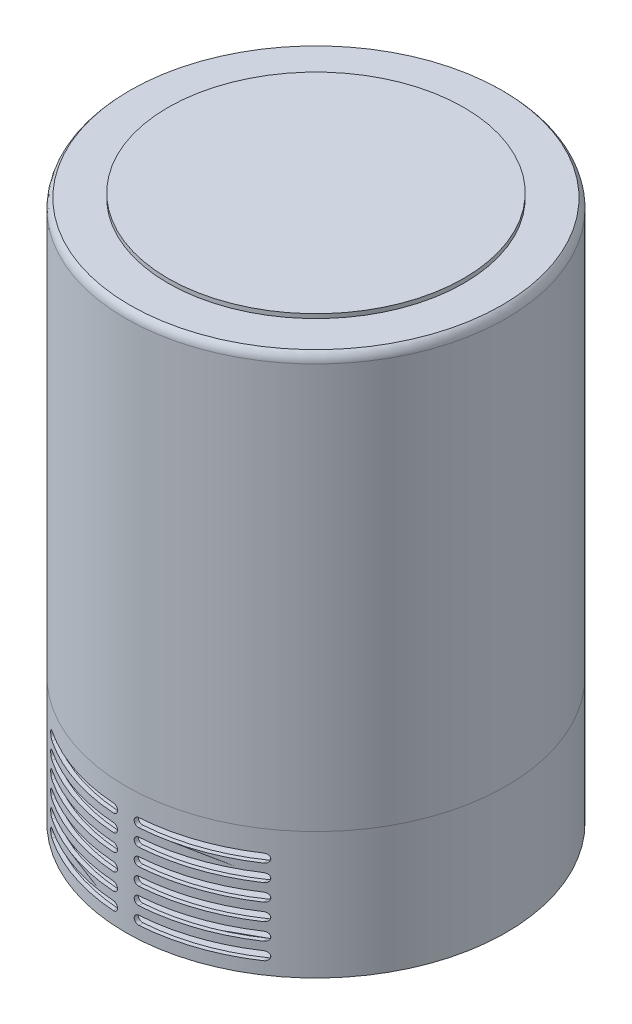
SolidWorks part; units mm, degrees
ref_plane "Front Plane" through (0, 0, 0) normal (0, 0, 1) x (1, 0, 0)
ref_plane "Top Plane" through (0, 0, 0) normal (0, 1, 0) x (1, 0, 0)
ref_plane "Right Plane" through (0, 0, 0) normal (1, 0, 0) x (0, 0, -1)
sketch "Sketch1" plane through (0, 0, 0) normal (0, 1, 0) x (1, 0, 0)
  circle A0 centre (0, 0) radius 45
  circle A1 centre (0, 0) radius 44
  dimension "D1" = 90
  dimension "D2" = 88
extrude "Boss-Extrude1" add sketch "Sketch1" along normal blind 98
fillet "Fillet1" radius 3 1 edges at (0, 98, 45)
sketch "Sketch13" plane through (0, 0, 0) normal (0, 1, 0) x (1, 0, 0)
  circle A0 centre (0, 0) radius 44
  dimension "D1" = 88
extrude "Boss-Extrude9" add sketch "Sketch13" along normal blind 2 from offset 96
sketch "Sketch5" plane through (0, 0, 0) normal (0, 1, 0) x (1, 0, 0)
  circle A0 centre (0, 0) radius 45
  dimension "D1" = 90
extrude "Boss-Extrude6" add sketch "Sketch5" against normal blind 30 separate body
sketch "Sketch6" plane through (0, 0, 0) normal (0, 1, 0) x (1, 0, 0)
  circle A0 centre (0, 0) radius 44
  dimension "D1" = 88
extrude "Cut-Extrude2" cut sketch "Sketch6" against normal blind 29
sketch "Sketch7" plane through (0, 98, 0) normal (0, 1, 0) x (1, 0, 0)
  circle A0 centre (0, 0) radius 35
  dimension "D1" = 70
extrude "Boss-Extrude7" add sketch "Sketch7" along normal blind 1
sketch "Sketch8" plane through (0, 0, 0) normal (1, 0, 0) x (0, 0, -1)
  line L0 (45, -15) -> (-47.6224, -15) construction
  line L1 (45, -30) -> (45, 0) construction
  line L3 (3.5, -16.75) -> (-3.5, -16.75)
  line L4 (3.5, -16.75) -> (3.5, -13.25)
  line L5 (3.5, -13.25) -> (-3.5, -13.25)
  line L6 (-3.5, -16.75) -> (-3.5, -13.25)
  line L7 (3.5, -16.75) -> (-3.5, -13.25) construction
  line L8 (3.5, -13.25) -> (-3.5, -16.75) construction
  point P4 (0, -15)
  dimension "D1" = 7
  dimension "D2" = 3.5
extrude "Cut-Extrude3" cut sketch "Sketch8" against normal through all from offset 39 offset against normal yes
sketch "Sketch10" plane through (0, 0, 0) normal (0, 0, 1) x (1, 0, 0)
  line L0 (25, -6.0288) -> (3, -6.0288) construction
  line L5 (0, 12.9357) -> (0, -57.2827) construction
  line L30 (25, -5) -> (3, -5)
  line L31 (25, -7.0576) -> (3, -7.0576)
  line L32 (-25, -6.0288) -> (-3, -6.0288) construction
  line L33 (-25, -5) -> (-3, -5)
  line L34 (-25, -7.0576) -> (-3, -7.0576)
  line L35 (-25, -10.0288) -> (-3, -10.0288) construction
  line L36 (-25, -9) -> (-3, -9)
  line L37 (-25, -11.0576) -> (-3, -11.0576)
  line L38 (25, -10.0288) -> (3, -10.0288) construction
  line L39 (25, -9) -> (3, -9)
  line L40 (25, -11.0576) -> (3, -11.0576)
  line L41 (-25, -14.0288) -> (-3, -14.0288) construction
  line L42 (-25, -13) -> (-3, -13)
  line L43 (-25, -15.0576) -> (-3, -15.0576)
  line L44 (25, -14.0288) -> (3, -14.0288) construction
  line L45 (25, -13) -> (3, -13)
  line L46 (25, -15.0576) -> (3, -15.0576)
  line L47 (-25, -18.0288) -> (-3, -18.0288) construction
  line L48 (-25, -17) -> (-3, -17)
  line L49 (-25, -19.0576) -> (-3, -19.0576)
  line L50 (25, -18.0288) -> (3, -18.0288) construction
  line L51 (25, -17) -> (3, -17)
  line L52 (25, -19.0576) -> (3, -19.0576)
  line L53 (-25, -22.0288) -> (-3, -22.0288) construction
  line L54 (-25, -21) -> (-3, -21)
  line L55 (-25, -23.0576) -> (-3, -23.0576)
  line L56 (25, -22.0288) -> (3, -22.0288) construction
  line L57 (25, -21) -> (3, -21)
  line L58 (25, -23.0576) -> (3, -23.0576)
  line L59 (-25, -26.0288) -> (-3, -26.0288) construction
  line L60 (-25, -25) -> (-3, -25)
  line L61 (-25, -27.0576) -> (-3, -27.0576)
  line L62 (25, -26.0288) -> (3, -26.0288) construction
  line L63 (25, -25) -> (3, -25)
  line L64 (25, -27.0576) -> (3, -27.0576)
  line L65 (45, 0) -> (-45, 0) construction
  arc A0 (-25, -5) -> (-25, -7.0576) centre (-25, -6.0288) ccw
  arc A1 (-3, -7.0576) -> (-3, -5) centre (-3, -6.0288) ccw
  arc A2 (25, -5) -> (25, -7.0576) centre (25, -6.0288) cw
  arc A3 (3, -7.0576) -> (3, -5) centre (3, -6.0288) cw
  arc A4 (-25, -9) -> (-25, -11.0576) centre (-25, -10.0288) ccw
  arc A5 (-3, -11.0576) -> (-3, -9) centre (-3, -10.0288) ccw
  arc A6 (25, -9) -> (25, -11.0576) centre (25, -10.0288) cw
  arc A7 (3, -11.0576) -> (3, -9) centre (3, -10.0288) cw
  arc A8 (-25, -13) -> (-25, -15.0576) centre (-25, -14.0288) ccw
  arc A9 (-3, -15.0576) -> (-3, -13) centre (-3, -14.0288) ccw
  arc A10 (25, -13) -> (25, -15.0576) centre (25, -14.0288) cw
  arc A11 (3, -15.0576) -> (3, -13) centre (3, -14.0288) cw
  arc A12 (-25, -17) -> (-25, -19.0576) centre (-25, -18.0288) ccw
  arc A13 (-3, -19.0576) -> (-3, -17) centre (-3, -18.0288) ccw
  arc A14 (25, -17) -> (25, -19.0576) centre (25, -18.0288) cw
  arc A15 (3, -19.0576) -> (3, -17) centre (3, -18.0288) cw
  arc A16 (-25, -21) -> (-25, -23.0576) centre (-25, -22.0288) ccw
  arc A17 (-3, -23.0576) -> (-3, -21) centre (-3, -22.0288) ccw
  arc A18 (25, -21) -> (25, -23.0576) centre (25, -22.0288) cw
  arc A19 (3, -23.0576) -> (3, -21) centre (3, -22.0288) cw
  arc A20 (-25, -25) -> (-25, -27.0576) centre (-25, -26.0288) ccw
  arc A21 (-3, -27.0576) -> (-3, -25) centre (-3, -26.0288) ccw
  arc A22 (25, -25) -> (25, -27.0576) centre (25, -26.0288) cw
  arc A23 (3, -27.0576) -> (3, -25) centre (3, -26.0288) cw
  point P3 (14, -6.0288)
  point P7 (-14, -6.0288)
  point P19 (14, -10.0288)
  point P22 (-14, -10.0288)
  point P33 (14, -14.0288)
  point P36 (-14, -14.0288)
  point P47 (14, -18.0288)
  point P50 (-14, -18.0288)
  point P61 (14, -22.0288)
  point P64 (-14, -22.0288)
  point P75 (14, -26.0288)
  point P78 (-14, -26.0288)
  dimension "D1" = 22
  dimension "D2" = 6
  dimension "D3" = 5
extrude "Cut-Extrude5" cut sketch "Sketch10" against normal blind 10 from offset 36 offset against normal yes
sketch "Sketch12" plane through (0, 0, 0) normal (0, 0, 1) x (1, 0, 0)
  line L0 (25, -6.0288) -> (3, -6.0288) construction
  line L5 (0, 12.9357) -> (0, -57.2827) construction
  line L30 (25, -5) -> (3, -5)
  line L31 (25, -7.0576) -> (3, -7.0576)
  line L32 (-25, -6.0288) -> (-3, -6.0288) construction
  line L33 (-25, -5) -> (-3, -5)
  line L34 (-25, -7.0576) -> (-3, -7.0576)
  line L35 (-25, -10.0288) -> (-3, -10.0288) construction
  line L36 (-25, -9) -> (-3, -9)
  line L37 (-25, -11.0576) -> (-3, -11.0576)
  line L38 (25, -10.0288) -> (3, -10.0288) construction
  line L39 (25, -9) -> (3, -9)
  line L40 (25, -11.0576) -> (3, -11.0576)
  line L41 (-25, -14.0288) -> (-3, -14.0288) construction
  line L42 (-25, -13) -> (-3, -13)
  line L43 (-25, -15.0576) -> (-3, -15.0576)
  line L44 (25, -14.0288) -> (3, -14.0288) construction
  line L45 (25, -13) -> (3, -13)
  line L46 (25, -15.0576) -> (3, -15.0576)
  line L47 (-25, -18.0288) -> (-3, -18.0288) construction
  line L48 (-25, -17) -> (-3, -17)
  line L49 (-25, -19.0576) -> (-3, -19.0576)
  line L50 (25, -18.0288) -> (3, -18.0288) construction
  line L51 (25, -17) -> (3, -17)
  line L52 (25, -19.0576) -> (3, -19.0576)
  line L53 (-25, -22.0288) -> (-3, -22.0288) construction
  line L54 (-25, -21) -> (-3, -21)
  line L55 (-25, -23.0576) -> (-3, -23.0576)
  line L56 (25, -22.0288) -> (3, -22.0288) construction
  line L57 (25, -21) -> (3, -21)
  line L58 (25, -23.0576) -> (3, -23.0576)
  line L59 (-25, -26.0288) -> (-3, -26.0288) construction
  line L60 (-25, -25) -> (-3, -25)
  line L61 (-25, -27.0576) -> (-3, -27.0576)
  line L62 (25, -26.0288) -> (3, -26.0288) construction
  line L63 (25, -25) -> (3, -25)
  line L64 (25, -27.0576) -> (3, -27.0576)
  line L65 (45, 0) -> (-45, 0) construction
  arc A0 (-25, -5) -> (-25, -7.0576) centre (-25, -6.0288) ccw
  arc A1 (-3, -7.0576) -> (-3, -5) centre (-3, -6.0288) ccw
  arc A2 (25, -5) -> (25, -7.0576) centre (25, -6.0288) cw
  arc A3 (3, -7.0576) -> (3, -5) centre (3, -6.0288) cw
  arc A4 (-25, -9) -> (-25, -11.0576) centre (-25, -10.0288) ccw
  arc A5 (-3, -11.0576) -> (-3, -9) centre (-3, -10.0288) ccw
  arc A6 (25, -9) -> (25, -11.0576) centre (25, -10.0288) cw
  arc A7 (3, -11.0576) -> (3, -9) centre (3, -10.0288) cw
  arc A8 (-25, -13) -> (-25, -15.0576) centre (-25, -14.0288) ccw
  arc A9 (-3, -15.0576) -> (-3, -13) centre (-3, -14.0288) ccw
  arc A10 (25, -13) -> (25, -15.0576) centre (25, -14.0288) cw
  arc A11 (3, -15.0576) -> (3, -13) centre (3, -14.0288) cw
  arc A12 (-25, -17) -> (-25, -19.0576) centre (-25, -18.0288) ccw
  arc A13 (-3, -19.0576) -> (-3, -17) centre (-3, -18.0288) ccw
  arc A14 (25, -17) -> (25, -19.0576) centre (25, -18.0288) cw
  arc A15 (3, -19.0576) -> (3, -17) centre (3, -18.0288) cw
  arc A16 (-25, -21) -> (-25, -23.0576) centre (-25, -22.0288) ccw
  arc A17 (-3, -23.0576) -> (-3, -21) centre (-3, -22.0288) ccw
  arc A18 (25, -21) -> (25, -23.0576) centre (25, -22.0288) cw
  arc A19 (3, -23.0576) -> (3, -21) centre (3, -22.0288) cw
  arc A20 (-25, -25) -> (-25, -27.0576) centre (-25, -26.0288) ccw
  arc A21 (-3, -27.0576) -> (-3, -25) centre (-3, -26.0288) ccw
  arc A22 (25, -25) -> (25, -27.0576) centre (25, -26.0288) cw
  arc A23 (3, -27.0576) -> (3, -25) centre (3, -26.0288) cw
  point P3 (14, -6.0288)
  point P7 (-14, -6.0288)
  point P19 (14, -10.0288)
  point P22 (-14, -10.0288)
  point P33 (14, -14.0288)
  point P36 (-14, -14.0288)
  point P47 (14, -18.0288)
  point P50 (-14, -18.0288)
  point P61 (14, -22.0288)
  point P64 (-14, -22.0288)
  point P75 (14, -26.0288)
  point P78 (-14, -26.0288)
  dimension "D1" = 22
  dimension "D2" = 6
  dimension "D3" = 5
extrude "Cut-Extrude6" cut sketch "Sketch12" against normal blind 10 from offset 46
